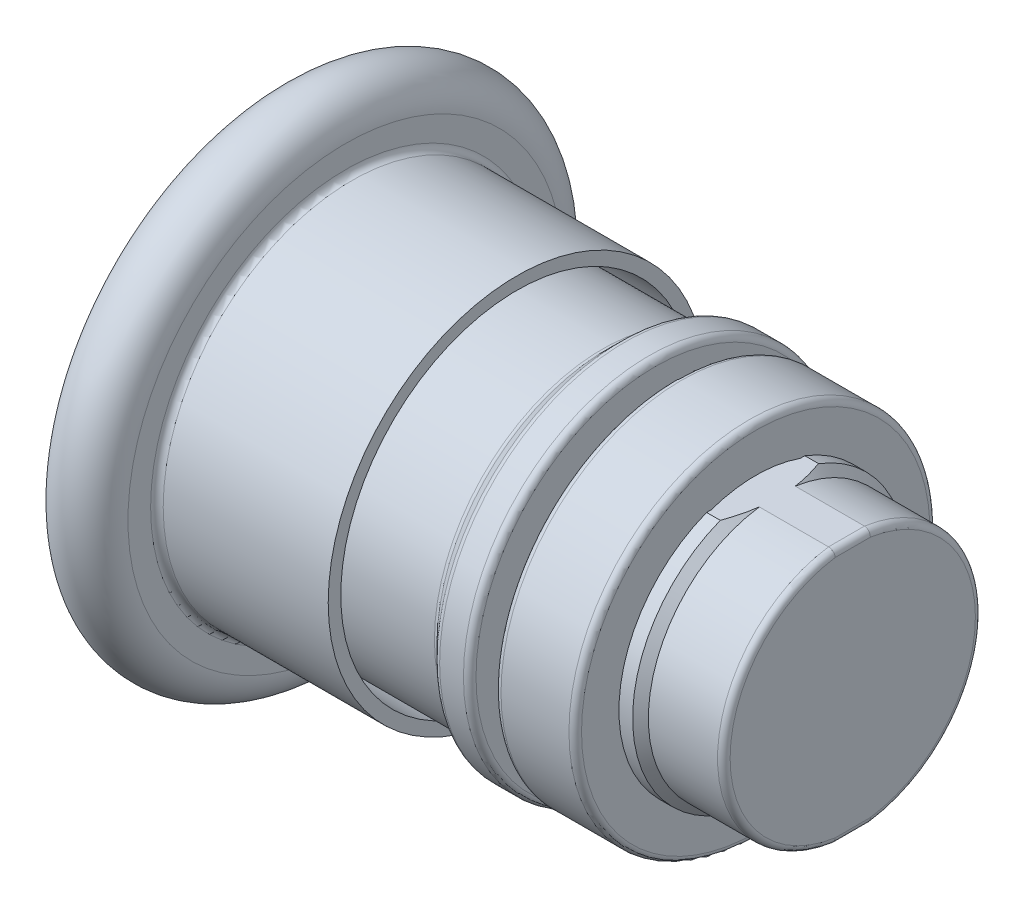
SolidWorks part; units mm, degrees
ref_plane "Front Plane" through (0, 0, 0) normal (0, 0, 1) x (1, 0, 0)
ref_plane "Top Plane" through (0, 0, 0) normal (0, 1, 0) x (1, 0, 0)
ref_plane "Right Plane" through (0, 0, 0) normal (1, 0, 0) x (0, 0, -1)
sketch "Sketch1" plane through (0, 0, 0) normal (0, 0, 1) x (1, 0, 0)
  line L0 (0, 0) -> (-20, 0) construction
  line L1 (-13.6174, 17.3) -> (-13.6174, 15)
  line L2 (-13.6174, 15) -> (0, 15)
  arc A0 (-20, 0) -> (-19, 17.6057) centre (135.4809, 0) cw
  arc A1 (-19, 17.6057) -> (-13.6174, 17.3) centre (-16.3174, 17.3) cw
  point P7 (-14.4765, 15)
  point P10 (0, 0)
  dimension "D2" = 40
  dimension "D4" = 2.7
  dimension "D1" = 20
  dimension "D3" = 30
  dimension "D5" = 1
revolve "Revolve-Thin1" add sketch "Sketch1" angle 360 about L0
sketch "Sketch2" plane through (0, 0, 0) normal (0, 0, 1) x (1, 0, 0)
  line L0 (0, 0) -> (26.7, 0) construction
  line L1 (26.7, 0) -> (26.7, 10.25)
  line L2 (26.7, 10.25) -> (20.7, 10.25)
  line L3 (20.7, 10.25) -> (20.075, 10.875)
  line L4 (20.075, 10.875) -> (11, 10.875)
  line L5 (11, 10.875) -> (11, 14.75)
  line L6 (11, 14.75) -> (8.4, 14.75)
  line L7 (8.4, 14.75) -> (7, 13.35)
  line L8 (7, 13.35) -> (-13.6174, 13.35)
  line L9 (-13.6174, 13.35) -> (-13.6174, 0)
  line L10 (-13.6174, -15) -> (-13.6174, 15) construction
  line L11 (26.7, 0) -> (-13.6174, 0)
  arc A0 (-19, 17.6057) -> (-19, -17.6057) centre (135.4809, 0) ccw construction
  point P3 (0, 0)
  point P13 (41.6429, 0)
  point P17 (2.6834, 13.35)
  point P18 (6.3625, 10.875)
  point P19 (12.7642, 10.875)
  dimension "D9" = 31
  dimension "D1" = 20.5
  dimension "D2" = 21.75
  dimension "D3" = 29.5
  dimension "D4" = 26.7
  dimension "D5" = 46.7
  dimension "D6" = 45
  dimension "D7" = 6
  dimension "D8" = 4
revolve "Revolve1" add sketch "Sketch2" angle 360 about L0
sketch "Sketch4" plane through (26.7, 0, 0) normal (1, 0, 0) x (0, 0, -1)
  line L0 (-3.9042, 10.15) -> (3.9042, 10.15)
  line L1 (-3.9042, -10.15) -> (3.9042, -10.15)
  circle A0 centre (0, 0) radius 10.875 construction
  arc A1 (3.9042, 10.15) -> (-3.9042, 10.15) centre (0, 0) ccw
  arc A2 (-3.9042, -10.15) -> (3.9042, -10.15) centre (0, 0) ccw
  dimension "D1" = 20.3
extrude "Cut-Extrude1" cut sketch "Sketch4" against normal up to surface (15.7 mm away) up to face at (11, 0, 14.75)
sketch "Sketch3" plane through (0, 0, 0) normal (0, 0, 1) x (1, 0, 0)
  line L0 (0, 0) -> (26.7, 0) construction
  line L1 (12.5875, 10.75) -> (18.9875, 10.75)
  line L2 (12.5875, 10.75) -> (12.5875, 14.35)
  line L3 (12.5875, 14.35) -> (18.9875, 14.35)
  line L4 (18.9875, 10.75) -> (18.9875, 14.35)
  line L5 (26.7, -10.25) -> (26.7, 10.25) construction
  line L7 (11, -14.75) -> (11, 14.75) construction
  point P9 (16.2526, 11.2508)
  dimension "D1" = 1.5875
  dimension "D2" = 6.4
  dimension "D3" = 28.7
  dimension "D4" = 21.5
revolve "Revolve2" add sketch "Sketch3" angle 360 about L0
fillet "Fillet1" radius 0.5 9 edges at (26.7, 0, -10.25) (26.7, 0, 10.25) (26.7, 10.15, 0) (26.7, -10.15, 0) (12.5875, 0, 14.35) (18.9875, 0, 14.35) (7, 0, 13.35) (8.4, 0, 14.75) (11, 0, 14.75)
fillet "Fillet2" radius 0.5 1 edges at (-13.6174, 0, -15)
